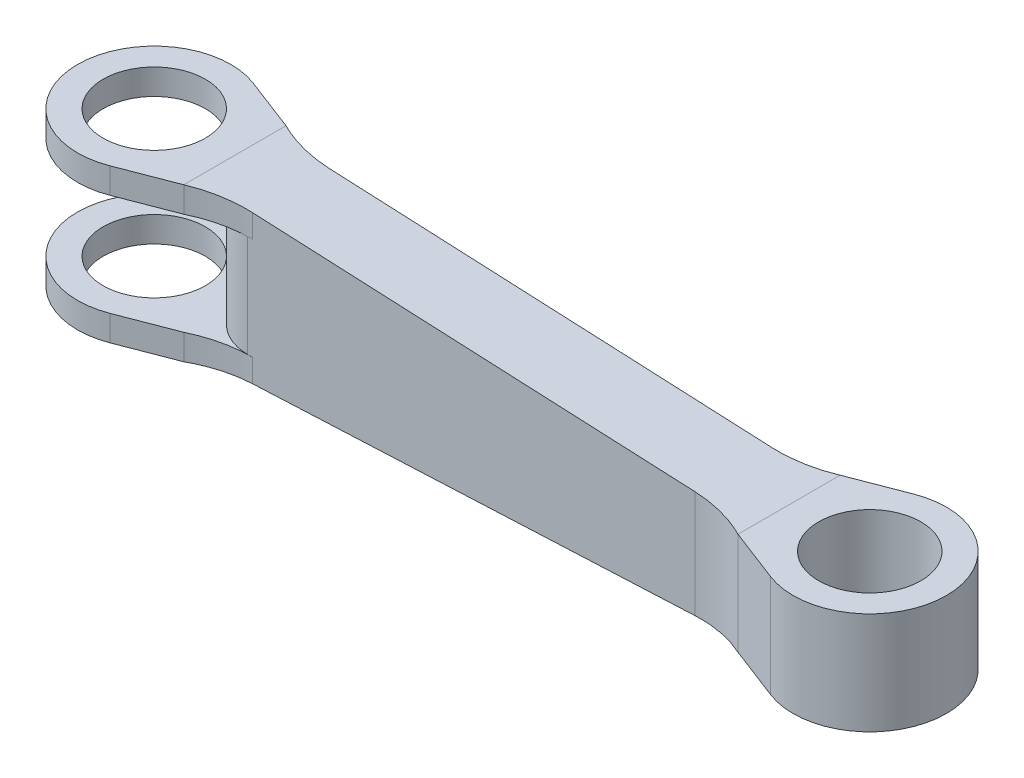
SolidWorks part; units mm, degrees
ref_plane "Front Plane" through (0, 0, 0) normal (0, 0, 1) x (1, 0, 0)
ref_plane "Top Plane" through (0, 0, 0) normal (0, 1, 0) x (1, 0, 0)
ref_plane "Right Plane" through (0, 0, 0) normal (1, 0, 0) x (0, 0, -1)
sketch "Sketch1" plane through (0, 0, 0) normal (0, 1, 0) x (1, 0, 0)
  line L0 (0, 0) -> (71.12, 0) construction
  line L1 (35.56, -22.8401) -> (35.56, 22.8401) construction
  line L2 (2.7357, 7.112) -> (8.0183, 5.08)
  line L3 (8.0183, 5.08) -> (8.0183, 3.81)
  line L4 (8.0183, 3.81) -> (63.1017, 3.81)
  line L5 (63.1017, 3.81) -> (63.1017, 5.08)
  line L6 (63.1017, 5.08) -> (68.3843, 7.112)
  line L7 (63.1017, -5.08) -> (68.3843, -7.112)
  line L8 (63.1017, -3.81) -> (63.1017, -5.08)
  line L9 (8.0183, -3.81) -> (63.1017, -3.81)
  line L10 (8.0183, -5.08) -> (8.0183, -3.81)
  line L11 (2.7357, -7.112) -> (8.0183, -5.08)
  circle A0 centre (0, 0) radius 5.08
  circle A1 centre (71.12, 0) radius 5.08
  arc A2 (2.7357, 7.112) -> (2.7357, -7.112) centre (0, 0) ccw
  arc A3 (68.3843, 7.112) -> (68.3843, -7.112) centre (71.12, 0) cw
  point P16 (35.56, 0)
  dimension "D1" = 10.16
  dimension "D3" = 2.54
  dimension "D4" = 2.54
  dimension "D2" = 71.12
  dimension "D5" = 3.81
  dimension "D6" = 1.27
  dimension "D7" = 2.032
extrude "Boss-Extrude1" add sketch "Sketch1" along normal mid plane 15.24
ref_plane "Plane1" through (0, 0, 13.97) normal (0, 0, 1) x (1, 0, 0)
sketch "Sketch2" plane through (0, 0, 13.97) normal (0, 0, 1) x (1, 0, 0)
  line L0 (-7.62, 7.62) -> (8.0183, 7.62) construction
  line L1 (8.0183, 7.62) -> (63.1017, 7.62) construction
  line L2 (8.0183, 7.62) -> (63.1017, 5.08)
  line L3 (63.1017, 5.08) -> (78.74, 5.08)
  line L4 (78.74, -7.62) -> (78.74, 7.62) construction
  line L5 (0, 0) -> (40.6246, 0) construction
  line L6 (-7.62, 7.62) -> (-7.62, -7.62) construction
  line L7 (-7.62, 5.08) -> (8.0183, 5.08)
  line L8 (-7.62, 5.08) -> (-7.62, -5.08)
  line L9 (-7.62, -5.08) -> (8.0183, -5.08)
  line L10 (8.0183, 5.08) -> (8.0183, -5.08)
  line L11 (8.0183, 7.62) -> (8.0183, -7.62) construction
  line L12 (8.0183, 7.62) -> (78.74, 7.62)
  line L13 (78.74, 7.62) -> (78.74, 5.08)
  line L14 (63.1017, -5.08) -> (78.74, -5.08)
  line L15 (-7.62, -7.62) -> (8.0183, -7.62) construction
  line L16 (78.74, -7.62) -> (78.74, -5.08)
  line L17 (8.0183, -7.62) -> (78.74, -7.62)
  line L18 (8.0183, -7.62) -> (63.1017, -5.08)
  point P22 (-7.62, 0)
  dimension "D1" = 2.54
  dimension "D2" = 2.54
extrude "Cut-Extrude1" cut sketch "Sketch2" against normal through all
fillet "Fillet1" radius 12.7 6 edges at (63.1017, 0, 3.81) (63.1017, 0, -3.81) (8.0183, -6.35, -3.81) (8.0183, 6.35, -3.81) (8.0183, -6.35, 3.81) (8.0183, 6.35, 3.81)
fillet "Fillet2" radius 5.08 2 edges at (8.0183, 0, -3.81) (8.0183, 0, 3.81)
